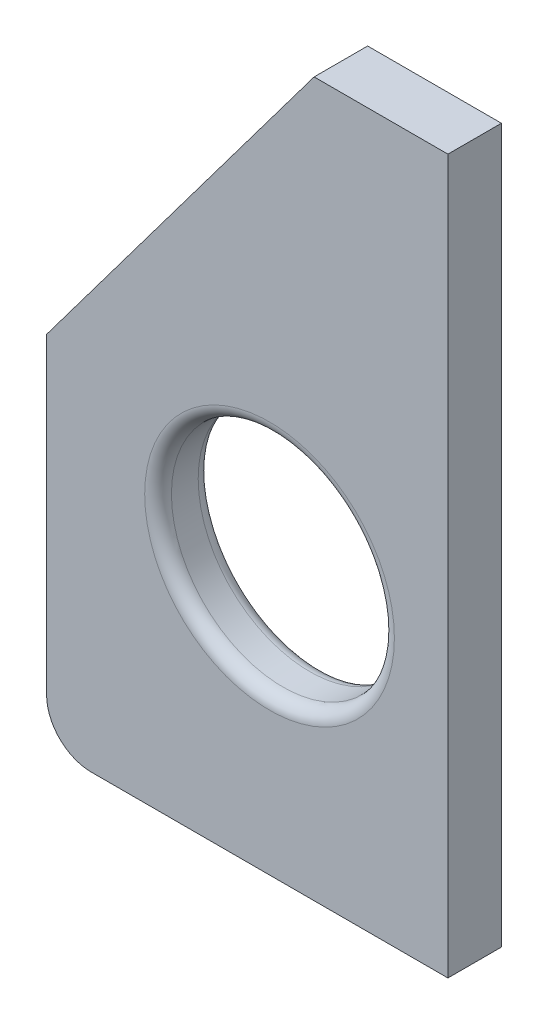
SolidWorks part; units mm, degrees
note: The reader was unsure of these and kept them because the rebuilt part matched: thickness of "基体-法兰1", "钣金(1)", "钣金(2)".
material "热轧钢板和钢带"
ref_plane "前视基准面" through (0, 0, 0) normal (0, 0, 1) x (1, 0, 0)
ref_plane "上视基准面" through (0, 0, 0) normal (0, 1, 0) x (1, 0, 0)
ref_plane "右视基准面" through (0, 0, 0) normal (1, 0, 0) x (0, 0, -1)
sketch "草图1" plane through (0, 0, 0) normal (0, 0, 1) x (1, 0, 0)
  line L0 (-30, 0) -> (-90, -80)
  line L1 (0, -160) -> (-80, -160)
  line L2 (0, -160) -> (0, 0)
  line L3 (0, 0) -> (-30, 0)
  line L4 (-90, -150) -> (-90, -80)
  arc A0 (-90, -150) -> (-80, -160) centre (-80, -150) ccw
  point P0 (0, 0)
  dimension "D3" = 10
  dimension "D4" = 80
  dimension "D5" = 90
  dimension "D1" = 160
  dimension "D2" = 30
  dimension "D6" = 80
base flange "基体-法兰1" sketch "草图1" thickness 12 reverse thickness direction no parameters "D1"=2
ref_plane "基准面1" through (0, 0, -6) normal (0, 0, 1) x (1, 0, 0)
ref_plane "基准面2" through (0, 0, -6) normal (0, 0, 1) x (1, 0, 0)
sketch "草图2" plane through (0, 0, 0) normal (0, 0, 1) x (1, 0, 0)
  line L0 (0, -160) -> (0, 0) construction
  line L3 (-80, -160) -> (0, -160) construction
  circle A0 centre (-40, -100) radius 25
  dimension "D1" = 50
  dimension "D2" = 40
  dimension "D3" = 60
extrude "切除-拉伸1" cut sketch "草图2" against normal through all normal cut yes
fillet "圆角1" radius 3 2 edges at (-15, -100, -12) (-15, -100, 0)
sketch "折弯-线1" plane through (0, 0, 0) normal (0, 1, 0) x (1, 0, 0)
sketch "边界框1" plane through (0, 0, 0) normal (0, 1, 0) x (1, 0, 0)
sheet metal parameters "钣金(1)" thickness 12 parameters "D1"=2
flat pattern "平板型式(1)" [suppressed]
sketch "折弯-线2" plane through (0, 0, 0) normal (0, 1, 0) x (1, 0, 0)
sketch "边界框2" [suppressed] plane through (0, 0, 0) normal (0, 1, 0) x (1, 0, 0)
sheet metal parameters "钣金(2)" thickness 12 parameters "D1"=2, "D7"=10
flat pattern "平板型式(1)"
sketch "折弯-线2" plane through (0, 0, 0) normal (0, 1, 0) x (1, 0, 0)
sketch "边界框2" [suppressed] plane through (0, 0, 0) normal (0, 1, 0) x (1, 0, 0)
